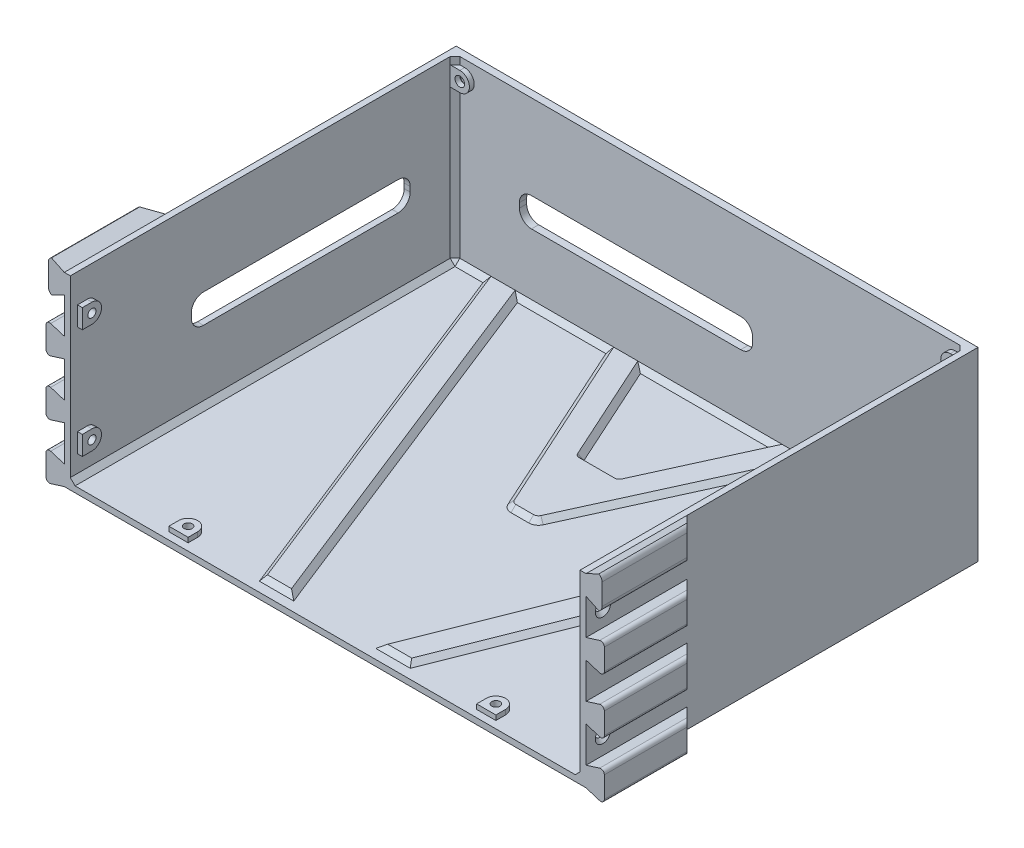
SolidWorks part; units mm, degrees
ref_plane "Płaszczyzna przednia" through (0, 0, 0) normal (0, 0, 1) x (1, 0, 0)
ref_plane "Płaszczyzna górna" through (0, 0, 0) normal (0, 1, 0) x (1, 0, 0)
ref_plane "Płaszczyzna prawa" through (0, 0, 0) normal (1, 0, 0) x (0, 0, -1)
sketch "Szkic1" plane through (0, 0, 0) normal (0, 0, 1) x (1, 0, 0)
  line L1 (0, 0) -> (217, 0)
  line L2 (0, 0) -> (0, 77.16)
  line L3 (0, 77.16) -> (217, 77.16)
  line L4 (217, 0) -> (217, 77.16)
  dimension "D1" = 77.16
  dimension "D2" = 217
extrude "Dodanie-wyciągnięcie1" add sketch "Szkic1" along normal blind 3
sketch "Szkic2" plane through (0, 0, 3) normal (0, 0, 1) x (1, 0, 0)
  line L0 (0, 77.16) -> (0, 0)
  line L1 (0, 0) -> (217, 0)
  line L2 (217, 0) -> (217, 77.16)
  line L3 (217, 77.16) -> (214.5, 77.16)
  line L4 (217, 77.16) -> (0, 77.16) construction
  line L5 (214.5, 77.16) -> (214.5, 2.5)
  line L6 (214.5, 2.5) -> (2.5, 2.5)
  line L7 (2.5, 2.5) -> (2.5, 77.16)
  line L8 (2.5, 77.16) -> (0, 77.16)
  dimension "D1" = 2.5
  dimension "D2" = 2.5
  dimension "D3" = 2.5
extrude "Dodanie-wyciągnięcie2" add sketch "Szkic2" along normal blind 160
sketch "Szkic3" plane through (0, 2.5, 0) normal (0, 1, 0) x (1, 0, 0)
  line L0 (17.5, -3) -> (78.5, -157)
  line L1 (214.5, -3) -> (2.5, -3) construction
  line L3 (27.5, -3) -> (88.5, -157)
  line L4 (214.5, -3) -> (2.5, -3) construction
  line L5 (101.1515, -50) -> (115.8485, -50)
  line L6 (78.5, -157) -> (88.5, -157)
  line L7 (17.5, -3) -> (27.5, -3)
  line L8 (199.5, -3) -> (138.5, -157)
  line L9 (138.5, -157) -> (128.5, -157)
  line L10 (128.5, -157) -> (138.5, -157)
  line L11 (128.5, -157) -> (189.5, -3)
  line L12 (189.5, -3) -> (199.5, -3)
  line L13 (217, 0) -> (0, 0) construction
  line L14 (68.5, -3) -> (102.9671, -78.8276)
  line L15 (114.0329, -78.8276) -> (148.5, -3)
  line L16 (138.5, -3) -> (117.6693, -48.8276)
  line L17 (99.3307, -48.8276) -> (78.5, -3)
  line L18 (104.7878, -80) -> (112.2122, -80)
  line L19 (68.5, -3) -> (78.5, -3)
  line L20 (138.5, -3) -> (148.5, -3)
  line L21 (108.5, 0) -> (108.5, -100) construction
  line L23 (214.5, -163) -> (2.5, -163) construction
  arc A0 (115.8485, -50) -> (117.6693, -48.8276) centre (115.8485, -48) ccw
  arc A1 (101.1515, -50) -> (99.3307, -48.8276) centre (101.1515, -48) cw
  arc A2 (112.2122, -80) -> (114.0329, -78.8276) centre (112.2122, -78) ccw
  arc A3 (104.7878, -80) -> (102.9671, -78.8276) centre (104.7878, -78) cw
  point P14 (108.5, 0)
  point P33 (113.5, -80)
  point P36 (103.5, -80)
  point P39 (108.5, -50)
  line M5 (214.5, -3) -> (2.5, -3)
  line M7 (2.5, -163) -> (214.5, -163)
  dimension "D16" = 2
  dimension "D1" = 20
  dimension "D2" = 15
  dimension "D3" = 40
  dimension "D4" = 10
  dimension "D5" = 15
  dimension "D6" = 10
  dimension "D7" = 10
  dimension "D8" = 10
  dimension "D9" = 10
  dimension "D10" = 10
  dimension "D11" = 10
  dimension "D12" = 5
  dimension "D13" = 60
  dimension "D14" = 80
  dimension "D15" = 30
  dimension "D17" = 6
extrude "Dodanie-wyciągnięcie3" add sketch "Szkic3" along normal blind 2 contours L3 L0 M5 M7 | L11 L8 M7 M5 | L20 L15 A2 L18 A3 L14 L19 L17 A1 L5 A0 L16 region at (53, 2.5, 80) region at (164, 2.5, 80)
chamfer "Sfazowanie2" distance 2 angle 45 25 edges at (169, 2.5, 80) (214.5, 39.83, 3) (214.5, 2.5, 83) (207, 2.5, 3) (58, 2.5, 80) (159, 2.5, 80) (169, 2.5, 3) (48, 2.5, 3) (48, 2.5, 80) (10, 2.5, 3) (2.5, 2.5, 83) (2.5, 39.83, 3) (108.5, 2.5, 3) (85.7335, 2.5, 40.9138) (103.7051, 2.5, 79.6815) (108.5, 2.5, 80) (113.2949, 2.5, 79.6815) (131.2665, 2.5, 40.9138) (128.0846, 2.5, 25.9138) (116.9313, 2.5, 49.6815) (108.5, 2.5, 50) (100.0687, 2.5, 49.6815) (88.9154, 2.5, 25.9138) (133.5, 2.5, 157) (83.5, 2.5, 157)
sketch "Szkic10" plane through (0, 0, 163) normal (0, 0, 1) x (1, 0, 0)
  line L0 (224.6, 87) -> (224.6, 0) construction
  line L1 (217, 0) -> (217, 77.16) construction
  line L2 (217, 0) -> (217, 8.16)
  line L3 (217, 0) -> (222.6526, -1.7665)
  line L4 (217, 8.16) -> (222.6526, 9.9265)
  line L5 (224.6, 8.4948) -> (224.6, -0.3348)
  line L6 (108.5, 77.16) -> (108.5, 114.4452) construction
  line L7 (212.5, 77.16) -> (4.5, 77.16) construction
  line L8 (217, 23) -> (217, 31.16)
  line L9 (217, 23) -> (222.6526, 21.2335)
  line L10 (217, 31.16) -> (222.6526, 32.9265)
  line L11 (224.6, 31.4948) -> (224.6, 22.6652)
  line L12 (217, 46) -> (217, 54.16)
  line L13 (217, 46) -> (222.6526, 44.2335)
  line L14 (217, 54.16) -> (222.6526, 55.9265)
  line L15 (224.6, 54.4948) -> (224.6, 45.6652)
  line L16 (-7.6, 54.4948) -> (-7.6, 45.6652)
  line L17 (0, 54.16) -> (-5.6526, 55.9265)
  line L18 (0, 46) -> (-5.6526, 44.2335)
  line L19 (0, 46) -> (0, 54.16)
  line L20 (-7.6, 31.4948) -> (-7.6, 22.6652)
  line L21 (0, 31.16) -> (-5.6526, 32.9265)
  line L22 (0, 23) -> (-5.6526, 21.2335)
  line L23 (0, 23) -> (0, 31.16)
  line L24 (-7.6, 8.4948) -> (-7.6, -0.3348)
  line L25 (0, 8.16) -> (-5.6526, 9.9265)
  line L26 (0, 0) -> (-5.6526, -1.7665)
  line L27 (0, 0) -> (0, 8.16)
  line L28 (217, 69) -> (217, 77.16)
  line L29 (217, 69) -> (222.3314, 66.4215)
  line L30 (217, 77.16) -> (222.3314, 79.7385)
  line L31 (223.6594, 77.4948) -> (223.6594, 68.6652)
  line L32 (-6.6594, 77.4948) -> (-6.6594, 68.6652)
  line L33 (0, 77.16) -> (-5.3314, 79.7385)
  line L34 (0, 69) -> (-5.3314, 66.4215)
  line L35 (0, 69) -> (0, 77.16)
  arc A0 (222.6526, -1.7665) -> (224.6, -0.3348) centre (223.1, -0.3348) ccw
  arc A1 (222.6526, 9.9265) -> (224.6, 8.4948) centre (223.1, 8.4948) cw
  arc A2 (222.6526, 21.2335) -> (224.6, 22.6652) centre (223.1, 22.6652) ccw
  arc A3 (222.6526, 32.9265) -> (224.6, 31.4948) centre (223.1, 31.4948) cw
  arc A4 (222.6526, 44.2335) -> (224.6, 45.6652) centre (223.1, 45.6652) ccw
  arc A5 (222.6526, 55.9265) -> (224.6, 54.4948) centre (223.1, 54.4948) cw
  arc A6 (-5.6526, 55.9265) -> (-7.6, 54.4948) centre (-6.1, 54.4948) ccw
  arc A7 (-5.6526, 44.2335) -> (-7.6, 45.6652) centre (-6.1, 45.6652) cw
  arc A8 (-5.6526, 32.9265) -> (-7.6, 31.4948) centre (-6.1, 31.4948) ccw
  arc A9 (-5.6526, 21.2335) -> (-7.6, 22.6652) centre (-6.1, 22.6652) cw
  arc A10 (-5.6526, 9.9265) -> (-7.6, 8.4948) centre (-6.1, 8.4948) ccw
  arc A11 (-5.6526, -1.7665) -> (-7.6, -0.3348) centre (-6.1, -0.3348) cw
  arc A12 (222.3314, 66.4215) -> (223.6594, 68.6652) centre (221.1, 68.6652) ccw
  arc A13 (222.3314, 79.7385) -> (223.6594, 77.4948) centre (221.1, 77.4948) cw
  arc A14 (-5.3314, 79.7385) -> (-6.6594, 77.4948) centre (-4.1, 77.4948) ccw
  arc A15 (-5.3314, 66.4215) -> (-6.6594, 68.6652) centre (-4.1, 68.6652) cw
  point P11 (224.6, -2.3751)
  point P14 (224.6, 10.5351)
  point P60 (-7.6, 10.5351)
  point P61 (-7.6, -2.3751)
  dimension "D5" = 1.5
  dimension "D1" = 7.6
  dimension "D2" = 8.16
  dimension "D3" = 23
  dimension "D4" = 34.71
  dimension "D6" = 3
extrude "Dodanie-wyciągnięcie6" add sketch "Szkic10" against normal blind 32
chamfer "Sfazowanie5" distance 10 angle 45 8 edges at (217, 50.08, 131) (217, 4.08, 131) (0, 4.08, 131) (0, 27.08, 131) (0, 50.08, 131) (217, 27.08, 131) (217, 73.08, 131) (0, 73.08, 131)
ref_plane "Płaszczyzna1" through (108.5, 0, 0) normal (-1, 0, 0) x (0, 0, 1)
sketch "Sketch1" plane through (0, 0, 0) normal (-1, 0, 0) x (0, 0, 1)
  line L0 (23.1472, 43.66) -> (111.1472, 43.66) construction
  line L13 (21.6472, 43.66) -> (112.6472, 43.66)
  line L14 (21.6472, 43.66) -> (21.6472, 31.66)
  line L15 (21.6472, 31.66) -> (112.6472, 31.66)
  line L16 (112.6472, 43.66) -> (112.6472, 31.66)
  line L17 (67.1472, 31.66) -> (67.1472, 43.66) construction
  line L18 (21.6472, 37.66) -> (112.6472, 37.66) construction
  line L19 (21.6472, 42.16) -> (21.6472, 33.16) construction
  line L20 (111.1472, 31.66) -> (23.1472, 31.66) construction
  line L21 (112.6472, 42.16) -> (112.6472, 33.16) construction
  point P4 (25.6776, 43.66)
  point P7 (21.6472, 34.0023)
  point P10 (103.8389, 31.66)
  point P13 (112.6472, 43.66)
  point P14 (107.3999, 43.66)
  point P15 (112.6472, 31.66)
  point P16 (112.6472, 37.66)
  point P89 (67.1472, 37.66)
extrude "Cut-Extrude1" cut sketch "Sketch1" against normal up to next contours L15 L16 L13 L14
sketch "Sketch2" plane through (0, 0, 0) normal (0, 0, -1) x (-1, 0, 0)
  line L0 (-30.7972, 29.96) -> (-124.7972, 29.96) construction
  line L1 (-126.2972, 41.96) -> (-29.2972, 41.96)
  line L2 (-126.2972, 41.96) -> (-126.2972, 29.96)
  line L3 (-126.2972, 29.96) -> (-29.2972, 29.96)
  line L5 (-29.2972, 41.96) -> (-29.2972, 29.96)
  line L6 (-77.7972, 29.96) -> (-77.7972, 41.96) construction
  line L7 (-126.2972, 35.96) -> (-29.2972, 35.96) construction
  line L12 (-29.2972, 40.46) -> (-29.2972, 31.46) construction
  line L13 (-124.7972, 41.96) -> (-30.7972, 41.96) construction
  line L14 (-126.2972, 31.46) -> (-126.2972, 40.46) construction
  point P4 (-31.9503, 29.96)
  point P7 (-29.0667, 29.96)
  point P8 (-29.2972, 38.3886)
  point P11 (-122.0641, 41.96)
  point P14 (-126.2972, 35.96)
  point P88 (-77.7972, 35.96)
extrude "Cut-Extrude2" cut sketch "Sketch2" against normal up to next contours L5 L1 L2 L3
sketch "Sketch3" plane through (217, 0, 0) normal (1, 0, 0) x (0, 0, -1)
  circle A0 centre (-156, 61.2082) radius 2 construction
  circle A1 centre (-156, 15.58) radius 2 construction
  circle A2 centre (-156, 61.2082) radius 2
  circle A3 centre (-156, 15.58) radius 2
sketch "Sketch4" plane through (0, 0, 0) normal (0, -1, 0) x (1, 0, 0)
  circle A1 centre (172.5, 156) radius 2 construction
  circle A2 centre (44.5, 156) radius 2 construction
  circle A3 centre (44.5, 156) radius 2
  circle A5 centre (172.5, 156) radius 2
  dimension "D1" = 4
sketch "Sketch5" plane through (0, 0, 0) normal (-1, 0, 0) x (0, 0, 1)
  circle A0 centre (156, 61.2082) radius 2 construction
  circle A1 centre (156, 15.58) radius 2 construction
  circle A2 centre (156, 61.2082) radius 2
  circle A3 centre (156, 15.58) radius 2
sketch "Sketch6" plane through (0, 0, 0) normal (-1, 0, 0) x (0, 0, 1)
  point P0 (156, 61.2082)
  point P3 (156, 15.58)
hole_wizard "CSK for M3 Countersunk Flat Head Screw1" positions "Sketch6" profile "Sketch7" countersink size "M3" standard "DIN" end condition up to next
sketch "Sketch7" plane through (0, 61.2082, 156) normal (0, 1, 0) x (0, 0, 1)
  line L0 (0, 0) -> (0, 2.5)
  line L1 (0, 2.5) -> (1.7, 2.5)
  line L2 (1.7, 2.5) -> (1.7, 1.45)
  line L3 (1.7, 1.45) -> (3.15, 0)
  line L5 (3.15, 0) -> (0, 0)
  line L6 (-1.7, 1.45) -> (-3.15, 0) construction
  line L11 (0, -6.35) -> (0, 107.95) construction
  dimension "Thru Hole Dia." = 3.4
  dimension "Thru Hole Depth" = 2.5
  dimension "Near C'Sink Dia." = 6.3
  dimension "Near C'Sink Angle" = 90
hole_wizard "CSK for M3 Countersunk Flat Head Screw2" positions "Sketch8" profile "Sketch9" countersink size "M3" standard "DIN" end condition up to next
sketch "Sketch8" plane through (0, 0, 0) normal (0, -1, 0) x (-1, 0, 0)
  point P0 (-44.5, -156)
  point P6 (-172.5, -156)
sketch "Sketch9" plane through (44.5, 0, 156) normal (1, 0, 0) x (0, 0, -1)
  line L0 (0, 0) -> (0, 2.5)
  line L1 (0, 2.5) -> (1.7, 2.5)
  line L2 (1.7, 2.5) -> (1.7, 1.45)
  line L3 (1.7, 1.45) -> (3.15, 0)
  line L5 (3.15, 0) -> (0, 0)
  line L6 (-1.7, 1.45) -> (-3.15, 0) construction
  line L11 (0, -6.35) -> (0, 107.95) construction
  dimension "Thru Hole Dia." = 3.4
  dimension "Thru Hole Depth" = 2.5
  dimension "Near C'Sink Dia." = 6.3
  dimension "Near C'Sink Angle" = 90
sketch "Sketch10" plane through (217, 0, 0) normal (1, 0, 0) x (0, 0, -1)
  point P0 (-156, 61.2082)
  point P3 (-156, 15.58)
hole_wizard "CSK for M3 Countersunk Flat Head Screw3" positions "Sketch10" profile "Sketch11" countersink size "M3" standard "DIN" end condition up to next
sketch "Sketch11" plane through (217, 61.2082, 156) normal (0, 1, 0) x (0, 0, -1)
  line L0 (0, 0) -> (0, 2.5)
  line L1 (0, 2.5) -> (1.7, 2.5)
  line L2 (1.7, 2.5) -> (1.7, 1.45)
  line L3 (1.7, 1.45) -> (3.15, 0)
  line L5 (3.15, 0) -> (0, 0)
  line L6 (-1.7, 1.45) -> (-3.15, 0) construction
  line L11 (0, -6.35) -> (0, 107.95) construction
  dimension "Thru Hole Dia." = 3.4
  dimension "Thru Hole Depth" = 2.5
  dimension "Near C'Sink Dia." = 6.3
  dimension "Near C'Sink Angle" = 90
sketch "Sketch12" plane through (0, 0, 0) normal (0, 0, -1) x (-1, 0, 0)
  circle A1 centre (-6.5, 70.16) radius 2 construction
  circle A2 centre (-210.5, 70.16) radius 2
  circle A3 centre (-6.5, 70.16) radius 2
  circle A4 centre (-210.5, 70.16) radius 2 construction
sketch "Sketch14" plane through (0, 0, 0) normal (0, 0, -1) x (-1, 0, 0)
  point P0 (-210.5, 70.16)
  point P3 (-6.5, 70.16)
hole_wizard "CSK for M3 Countersunk Flat Head Screw4" positions "Sketch14" profile "Sketch15" countersink size "M3" standard "DIN" end condition up to next
sketch "Sketch15" plane through (210.5, 70.16, 0) normal (1, 0, 0) x (0, 1, 0)
  line L0 (0, 0) -> (0, 3)
  line L1 (0, 3) -> (1.7, 3)
  line L2 (1.7, 3) -> (1.7, 1.45)
  line L3 (1.7, 1.45) -> (3.15, 0)
  line L5 (3.15, 0) -> (0, 0)
  line L6 (-1.7, 1.45) -> (-3.15, 0) construction
  line L11 (0, -6.35) -> (0, 107.95) construction
  dimension "Thru Hole Dia." = 3.4
  dimension "Thru Hole Depth" = 3
  dimension "Near C'Sink Dia." = 6.3
  dimension "Near C'Sink Angle" = 90
sketch "Sketch16" plane through (0, 2.5, 0) normal (0, 1, 0) x (1, 0, 0)
  line L0 (180.5, -160) -> (164.5, -160) construction
  line L1 (52.5, -160) -> (36.5, -160) construction
  line L2 (176.5, -160) -> (168.5, -160)
  line L3 (48.5, -160) -> (40.5, -160)
  line L4 (176.5, -156) -> (176.5, -160)
  line L5 (168.5, -156) -> (168.5, -160)
  line L6 (48.5, -156) -> (48.5, -160)
  line L7 (40.5, -156) -> (40.5, -160)
  arc A0 (172.5, -152) -> (168.5, -156) centre (172.5, -156) ccw construction
  arc A1 (176.5, -156) -> (172.5, -152) centre (172.5, -156) ccw construction
  circle A2 centre (172.5, -156) radius 1.7 construction
  circle A3 centre (172.5, -156) radius 1.7
  arc A4 (44.5, -152) -> (40.5, -156) centre (44.5, -156) ccw construction
  arc A5 (48.5, -156) -> (44.5, -152) centre (44.5, -156) ccw construction
  arc A8 (172.5, -152) -> (168.5, -156) centre (172.5, -156) ccw
  arc A9 (176.5, -156) -> (172.5, -152) centre (172.5, -156) ccw
  arc A12 (44.5, -152) -> (40.5, -156) centre (44.5, -156) ccw
  arc A13 (48.5, -156) -> (44.5, -152) centre (44.5, -156) ccw
  circle A16 centre (44.5, -156) radius 1.7 construction
  circle A18 centre (44.5, -156) radius 1.7
extrude "Boss-Extrude1" add sketch "Sketch16" along normal blind 2
sketch "Sketch18" plane through (214.5, 0, 0) normal (-1, 0, 0) x (0, 0, 1)
  line L0 (160, 69.2082) -> (160, 53.2082) construction
  line L1 (160, 23.58) -> (160, 7.58) construction
  line L2 (160, 65.2082) -> (160, 57.2082)
  line L3 (160, 19.5478) -> (160, 11.58)
  line L4 (156, 11.58) -> (160, 11.58)
  line L5 (156, 19.58) -> (160, 19.5478)
  line L6 (154.65, 19.5478) -> (163.15, 19.5478) construction
  line L7 (156, 57.2082) -> (160, 57.2082)
  line L8 (156, 65.2082) -> (160, 65.2082)
  circle A0 centre (156, 61.2082) radius 1.7 construction
  circle A1 centre (156, 15.58) radius 1.7 construction
  circle A2 centre (156, 61.2082) radius 1.7
  circle A3 centre (156, 15.58) radius 1.7
  arc A5 (152, 61.2082) -> (156, 57.2082) centre (156, 61.2082) ccw construction
  arc A6 (156, 65.2082) -> (152, 61.2082) centre (156, 61.2082) ccw construction
  arc A8 (152, 15.58) -> (156, 11.58) centre (156, 15.58) ccw construction
  arc A9 (156, 19.58) -> (152, 15.58) centre (156, 15.58) ccw construction
  arc A13 (152, 61.2082) -> (156, 57.2082) centre (156, 61.2082) ccw
  arc A14 (156, 65.2082) -> (152, 61.2082) centre (156, 61.2082) ccw
  arc A16 (152, 15.58) -> (156, 11.58) centre (156, 15.58) ccw
  arc A17 (156, 19.58) -> (152, 15.58) centre (156, 15.58) ccw
extrude "Boss-Extrude3" add sketch "Sketch18" along normal blind 2
sketch "Sketch19" plane through (0, 0, 3) normal (0, 0, 1) x (1, 0, 0)
  line L0 (214.5, 66.16) -> (210.5, 66.16) construction
  line L1 (202.5, 74.16) -> (214.5, 74.16) construction
  line L2 (214.5, 74.16) -> (214.5, 66.16) construction
  line L3 (2.5, 74.16) -> (14.5, 74.16) construction
  line L4 (6.5, 66.16) -> (2.5, 66.16) construction
  line L5 (2.5, 66.16) -> (2.5, 74.16) construction
  line L6 (214.5, 66.16) -> (210.5, 66.16)
  line L7 (210.5, 74.16) -> (214.5, 74.16)
  line L8 (214.5, 74.16) -> (214.5, 66.16)
  line L9 (2.5, 74.16) -> (6.5, 74.16)
  line L10 (6.5, 66.16) -> (2.5, 66.16)
  line L11 (2.5, 66.16) -> (2.5, 74.16)
  circle A0 centre (6.5, 70.16) radius 2 construction
  circle A1 centre (210.5, 70.16) radius 1.7 construction
  circle A2 centre (6.5, 70.16) radius 2
  circle A3 centre (210.5, 70.16) radius 1.7
  arc A4 (206.5, 70.16) -> (210.5, 66.16) centre (210.5, 70.16) ccw construction
  arc A7 (6.5, 66.16) -> (10.5, 70.16) centre (6.5, 70.16) ccw construction
  arc A8 (210.5, 74.16) -> (210.5, 66.16) centre (210.5, 70.16) ccw
  arc A11 (6.5, 66.16) -> (6.5, 74.16) centre (6.5, 70.16) ccw
extrude "Boss-Extrude4" add sketch "Sketch19" along normal blind 2
ref_plane "Plane1" through (108.5, 0, 0) normal (1, 0, 0) x (0, 0, -1)
mirror "Mirror1" about plane through (108.5, 0, 0) normal (1, 0, 0) of "Boss-Extrude3"
fillet "Fillet1" radius 5 8 edges at (1.25, 31.66, 112.6472) (1.25, 43.66, 112.6472) (1.25, 43.66, 21.6472) (1.25, 31.66, 21.6472) (29.2972, 29.96, 1.5) (29.2972, 41.96, 1.5) (126.2972, 41.96, 1.5) (126.2972, 29.96, 1.5)
